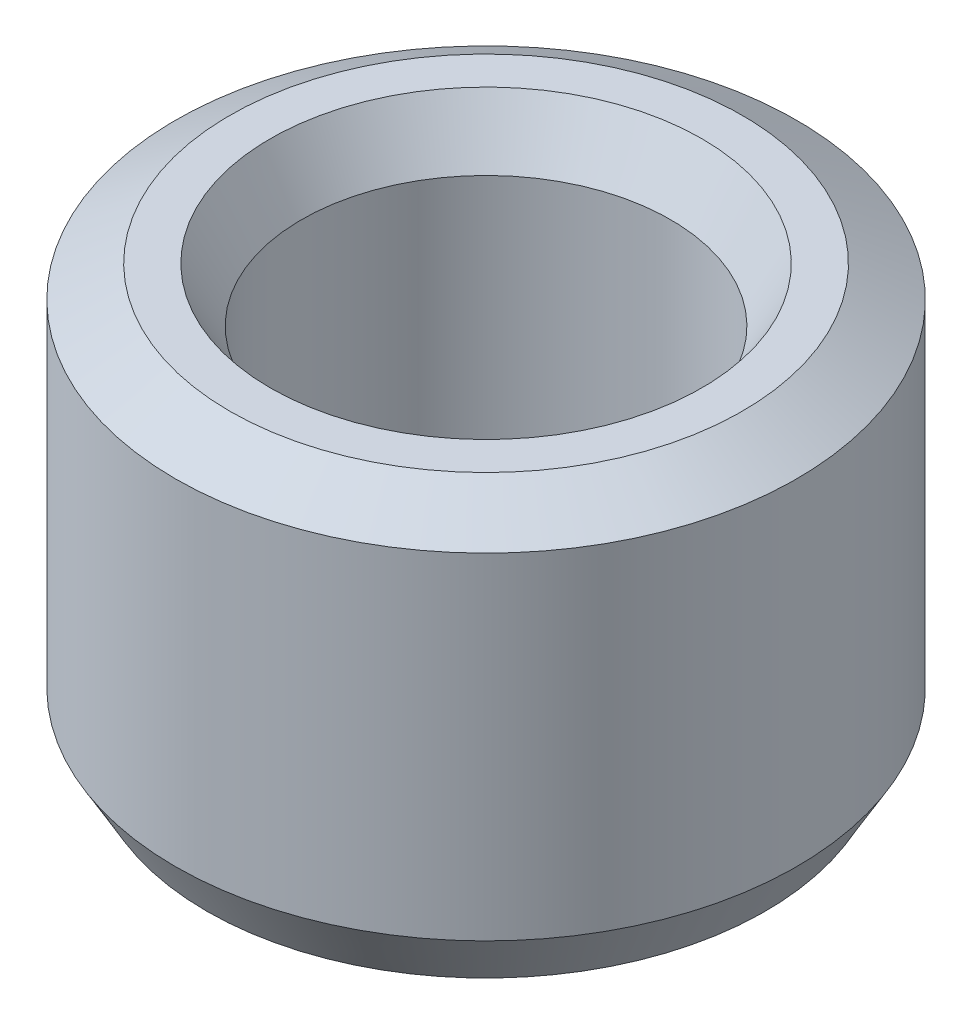
SolidWorks part; units mm, degrees
ref_plane "Front Plane" through (0, 0, 0) normal (0, 0, 1) x (1, 0, 0)
ref_plane "Top Plane" through (0, 0, 0) normal (0, 1, 0) x (1, 0, 0)
ref_plane "Right Plane" through (0, 0, 0) normal (1, 0, 0) x (0, 0, -1)
sketch "Sketch1" plane through (0, 0, 0) normal (0, 1, 0) x (1, 0, 0)
  circle A0 centre (0, 0) radius 15
  dimension "SLEEVE_OD" = 30
extrude "Boss-Extrude1" add sketch "Sketch1" along normal blind 20.3578
sketch "Sketch2" plane through (0, 0, 0) normal (0, 1, 0) x (1, 0, 0)
  circle A0 centre (0, 0) radius 8.9081
  dimension "BORE_D" = 17.8163
extrude "Cut-Extrude1" cut sketch "Sketch2" along normal through all
chamfer "Chamfer1" distance 1.5155 angle 60 4 edges at (0, 20.3578, 8.9081) (0, 0, 8.9081) (0, 0, 15) (0, 20.3578, 15) first distance on face at (0, 20.3578, 8.9081) first distance on face at (0, 0, 8.9081) first distance on face at (0, 20.3578, 15)
